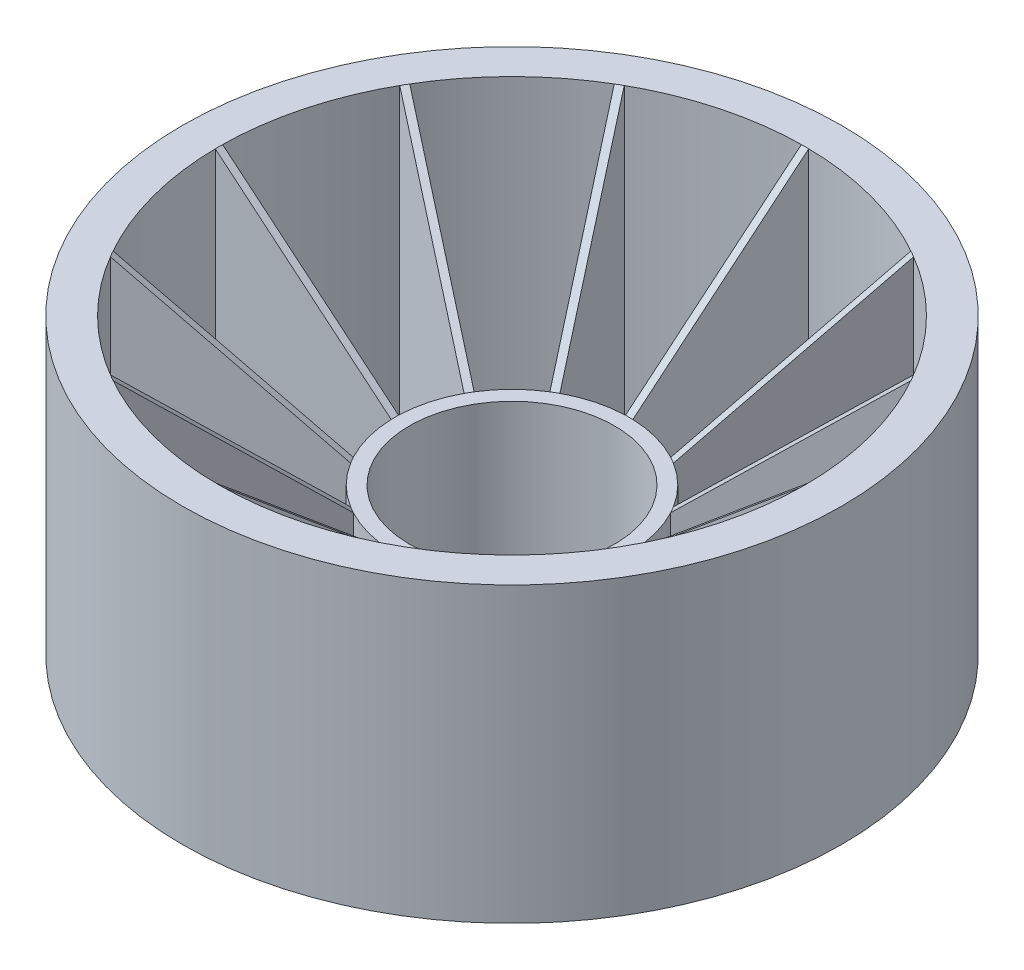
SolidWorks part; units mm, degrees
ref_plane "Front Plane" through (0, 0, 0) normal (0, 0, 1) x (1, 0, 0)
ref_plane "Top Plane" through (0, 0, 0) normal (0, 1, 0) x (1, 0, 0)
ref_plane "Right Plane" through (0, 0, 0) normal (1, 0, 0) x (0, 0, -1)
sketch "Sketch1" plane through (0, 0, 0) normal (0, 1, 0) x (1, 0, 0)
  circle A0 centre (0, 0) radius 25.4
  circle A1 centre (0, 0) radius 28.575
  dimension "D1" = 57.15
  dimension "D2" = 50.8
extrude "Boss-Extrude1" add sketch "Sketch1" along normal blind 25.4 contours A1 | A0
sketch "Sketch2" plane through (0, 0, 0) normal (0, 1, 0) x (1, 0, 0)
  circle A0 centre (0, 0) radius 10.16
  circle A1 centre (0, 0) radius 8.89
  dimension "D1" = 20.32
  dimension "D2" = 17.78
extrude "Boss-Extrude2" add sketch "Sketch2" along normal blind 12.7 separate body
sketch "Sketch4" plane through (0, 0, 0) normal (0, 1, 0) x (1, 0, 0)
  line L0 (12.425, 22.1558) -> (4.8026, 8.9533)
  line L1 (-0.3175, 25.4) -> (0.3175, 25.4)
  line L2 (-0.3175, 25.4) -> (-0.3175, 10.155)
  line L3 (-0.3175, 10.155) -> (0.3175, 10.155)
  line L4 (0.3175, 25.4) -> (0.3175, 10.155)
  line L5 (12.425, 22.1558) -> (12.975, 21.8383)
  line L6 (12.975, 21.8383) -> (5.3525, 8.6358)
  line L7 (4.8026, 8.9533) -> (5.3525, 8.6358)
  line L8 (21.8383, 12.975) -> (8.6358, 5.3525)
  line L9 (21.8383, 12.975) -> (22.1558, 12.425)
  line L10 (22.1558, 12.425) -> (8.9533, 4.8026)
  line L11 (8.6358, 5.3525) -> (8.9533, 4.8026)
  line L12 (25.4, 0.3175) -> (10.155, 0.3175)
  line L13 (25.4, 0.3175) -> (25.4, -0.3175)
  line L14 (25.4, -0.3175) -> (10.155, -0.3175)
  line L15 (10.155, 0.3175) -> (10.155, -0.3175)
  line L16 (22.1558, -12.425) -> (8.9533, -4.8026)
  line L17 (22.1558, -12.425) -> (21.8383, -12.975)
  line L18 (21.8383, -12.975) -> (8.6358, -5.3525)
  line L19 (8.9533, -4.8026) -> (8.6358, -5.3525)
  line L20 (12.975, -21.8383) -> (5.3525, -8.6358)
  line L21 (12.975, -21.8383) -> (12.425, -22.1558)
  line L22 (12.425, -22.1558) -> (4.8026, -8.9533)
  line L23 (5.3525, -8.6358) -> (4.8026, -8.9533)
  line L24 (0.3175, -25.4) -> (0.3175, -10.155)
  line L25 (0.3175, -25.4) -> (-0.3175, -25.4)
  line L26 (-0.3175, -25.4) -> (-0.3175, -10.155)
  line L27 (0.3175, -10.155) -> (-0.3175, -10.155)
  line L28 (-12.425, -22.1558) -> (-4.8026, -8.9533)
  line L29 (-12.425, -22.1558) -> (-12.975, -21.8383)
  line L30 (-12.975, -21.8383) -> (-5.3525, -8.6358)
  line L31 (-4.8026, -8.9533) -> (-5.3525, -8.6358)
  line L32 (-21.8383, -12.975) -> (-8.6358, -5.3525)
  line L33 (-21.8383, -12.975) -> (-22.1558, -12.425)
  line L34 (-22.1558, -12.425) -> (-8.9533, -4.8026)
  line L35 (-8.6358, -5.3525) -> (-8.9533, -4.8026)
  line L36 (-25.4, -0.3175) -> (-10.155, -0.3175)
  line L37 (-25.4, -0.3175) -> (-25.4, 0.3175)
  line L38 (-25.4, 0.3175) -> (-10.155, 0.3175)
  line L39 (-10.155, -0.3175) -> (-10.155, 0.3175)
  line L40 (-22.1558, 12.425) -> (-8.9533, 4.8026)
  line L41 (-22.1558, 12.425) -> (-21.8383, 12.975)
  line L42 (-21.8383, 12.975) -> (-8.6358, 5.3525)
  line L43 (-8.9533, 4.8026) -> (-8.6358, 5.3525)
  line L44 (-12.975, 21.8383) -> (-5.3525, 8.6358)
  line L45 (-12.975, 21.8383) -> (-12.425, 22.1558)
  line L46 (-12.425, 22.1558) -> (-4.8026, 8.9533)
  line L47 (-5.3525, 8.6358) -> (-4.8026, 8.9533)
  circle A0 centre (0, 0) radius 10.16 construction
  circle A1 centre (0, 0) radius 25.4 construction
  point P6 (0, 10.155)
  point P9 (0, 25.4)
  dimension "D2" = 0.635
  dimension "D1" = 12
extrude "Boss-Extrude3" add sketch "Sketch4" along normal up to surface (12.7 mm away) up to face at (0, 12.7, 10.16)
sketch "Sketch7" plane through (0, 0, 0) normal (0, 0, 1) x (1, 0, 0)
  line L0 (-10.155, 12.7) -> (-25.4, 25.4)
  line L1 (-25.4, 25.4) -> (-25.4, 12.7) construction
rib "Rib8" sketch "Sketch7" sketch "Sketch7" thickness 0.635 extrusion direction parallel to sketch draft on no parameters "D1"=0.635
ref_axis "Axis1" through (0, 26.6719, 0) along (0, -1, 0)
pattern_circular "CirPattern1" count 12 over 360 about axis through (0, 26.6719, 0) along (0, -1, 0) of "Rib8"
